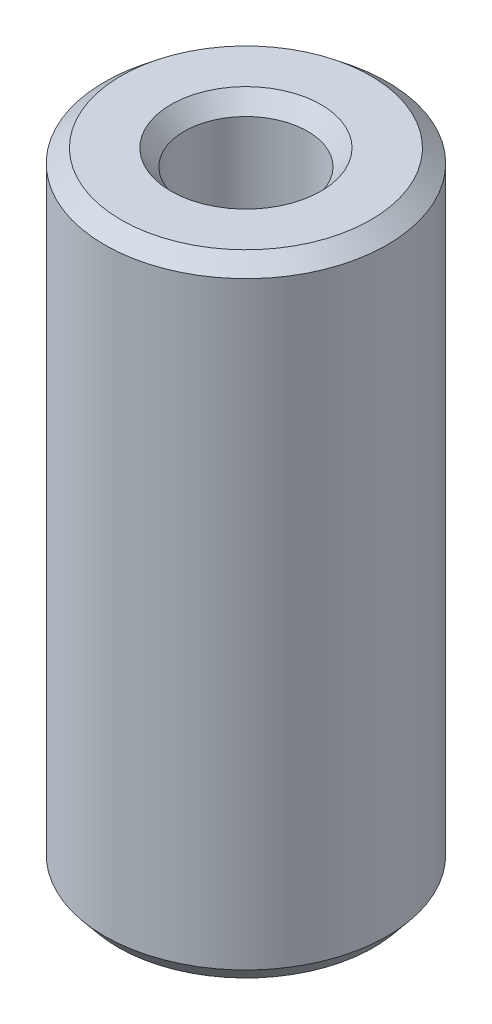
SolidWorks part; units mm, degrees
ref_plane "Front Plane" through (0, 0, 0) normal (0, 0, 1) x (1, 0, 0)
ref_plane "Top Plane" through (0, 0, 0) normal (0, 1, 0) x (1, 0, 0)
ref_plane "Right Plane" through (0, 0, 0) normal (1, 0, 0) x (0, 0, -1)
sketch "Sketch1" plane through (0, 0, 0) normal (0, 1, 0) x (1, 0, 0)
  circle A0 centre (0, 0) radius 20
  dimension "SLEEVE_OD" = 40
extrude "Boss-Extrude1" add sketch "Sketch1" along normal blind 88.9959
sketch "Sketch2" plane through (0, 0, 0) normal (0, 1, 0) x (1, 0, 0)
  circle A0 centre (0, 0) radius 8.7262
  dimension "BORE_D" = 17.4524
extrude "Cut-Extrude1" cut sketch "Sketch2" along normal through all
chamfer "Chamfer1" distance 1.9003 angle 50.739 4 edges at (0, 88.9959, 8.7262) (0, 0, 8.7262) (0, 0, 20) (0, 88.9959, 20) first distance on face at (0, 88.9959, 8.7262) first distance on face at (0, 0, 8.7262) first distance on face at (0, 88.9959, 20)
